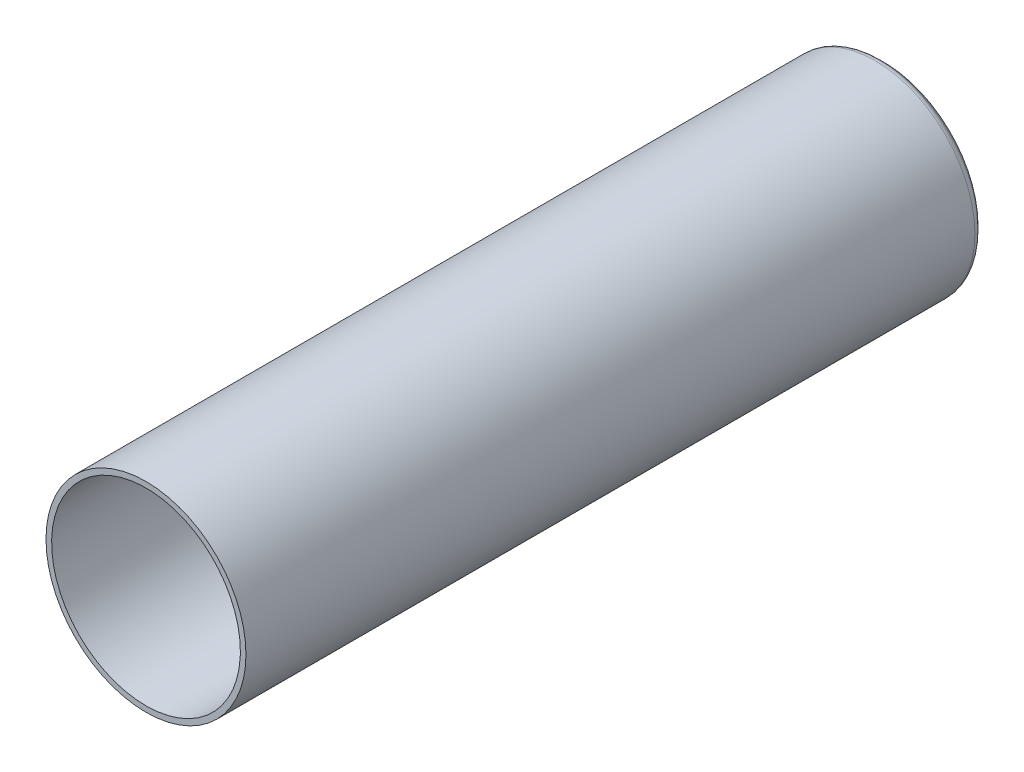
SolidWorks part; units mm, degrees
ref_plane "Front Plane" through (0, 0, 0) normal (0, 0, 1) x (1, 0, 0)
ref_plane "Top Plane" through (0, 0, 0) normal (0, 1, 0) x (1, 0, 0)
ref_plane "Right Plane" through (0, 0, 0) normal (1, 0, 0) x (0, 0, -1)
sketch "Sketch1" plane through (0, 0, 0) normal (0, 0, 1) x (1, 0, 0)
  circle A0 centre (0, 0) radius 12.6
  circle A1 centre (0, 0) radius 13.35
  dimension "D1" = 25.2
  dimension "D2" = 26.7
extrude "Boss-Extrude1" add sketch "Sketch1" along normal blind 97
sketch "Sketch2" plane through (0, 0, 0) normal (0, 0, -1) x (-1, 0, 0)
  circle A1 centre (0, 0) radius 13.35
  circle A2 centre (0, 0) radius 13.35
  dimension "D1" = 0
extrude "Boss-Extrude2" add sketch "Sketch2" along normal blind 1.5
sketch "Sketch3" plane through (0, 0, 0) normal (0, 1, 0) x (1, 0, 0)
  line L0 (-12.6, 0) -> (12.6, 0) construction
  line L1 (-12.6, 0) -> (12.6, 0)
  line L2 (12.6, 0) -> (12.6, -15.8916)
  line L3 (12.6, -15.8916) -> (11.4667, 0)
  point P3 (12.6, -9.4626)
  point P5 (12.6, -10.8143)
  point P6 (11.7885, -15.8916)
  point P7 (11.4667, 0)
extrude "Boss-Extrude3" add sketch "Sketch3" along normal mid plane 1.5 contours L3 L2 L1 region at (12.2222, 0, 5.2972)
fillet "Fillet1" radius 0.5 2 edges at (12.0222, 0.75, 7.7892) (12.0222, -0.75, 7.7892)
sketch "Sketch4" plane through (0, 0, 0) normal (0, 0, 1) x (1, 0, 0)
  circle A0 centre (0, 0) radius 4.5
  dimension "D1" = 9
extrude "Cut-Extrude1" cut sketch "Sketch4" against normal blind 1.5
chamfer "Chamfer1" distance 0.75 angle 45 2 edges at (-13.35, 0, -1.5) (4.5, 0, -1.5)
fillet "Fillet2" radius 1 2 edges at (-13.35, 0, -0.75) (-4.5, 0, -0.75)
